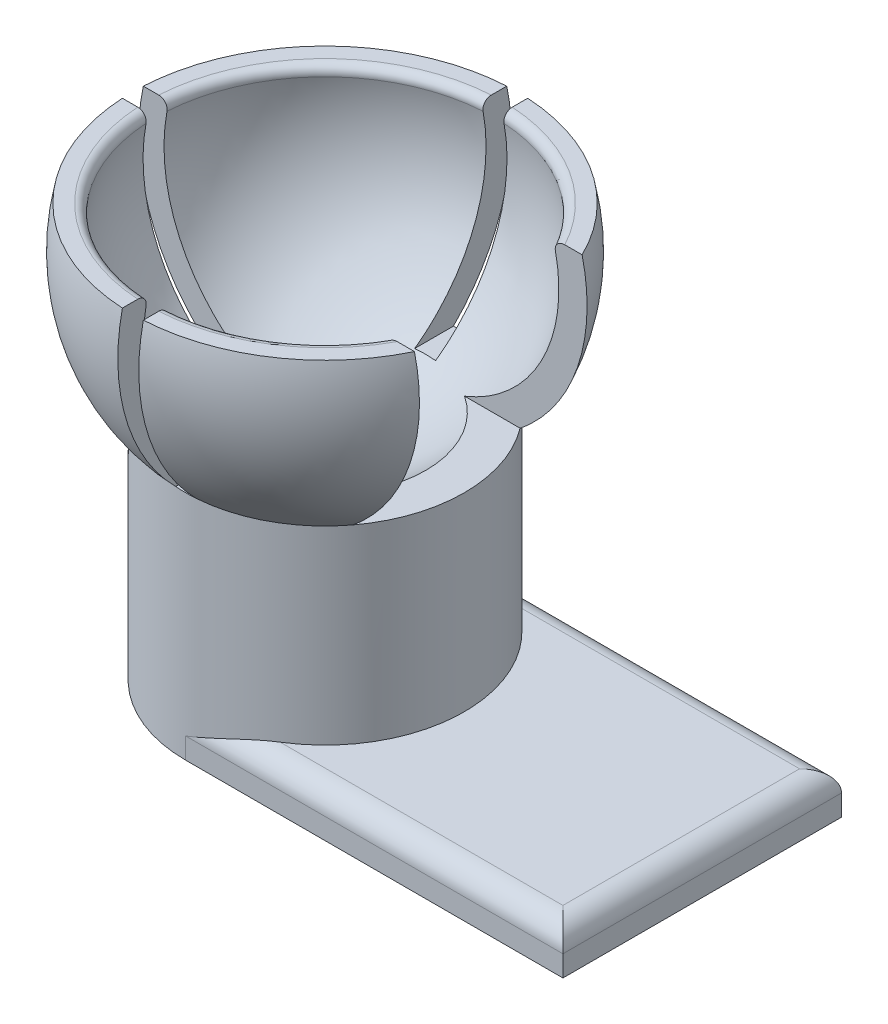
SolidWorks part; units mm, degrees
ref_plane "Front Plane" through (0, 0, 0) normal (0, 0, 1) x (1, 0, 0)
ref_plane "Top Plane" through (0, 0, 0) normal (0, 1, 0) x (1, 0, 0)
ref_plane "Right Plane" through (0, 0, 0) normal (1, 0, 0) x (0, 0, -1)
sketch "Sketch1" plane through (0, 0, 0) normal (0, 0, 1) x (1, 0, 0)
  line L0 (-9.1848, 2) -> (9.1848, 2)
  line L1 (0, 0) -> (0, 13.0891)
  line L2 (-6.6468, -6.6468) -> (-6.6468, -15.7)
  line L3 (-6.6468, -15.7) -> (6.6468, -15.7)
  line L4 (6.6468, -15.7) -> (6.6468, -6.6468)
  line L5 (0, 0) -> (6.6468, -6.6468) construction
  line L6 (0, 0) -> (-6.6468, -6.6468) construction
  circle A0 centre (0, 0) radius 8.2
  circle A1 centre (0, 0) radius 9.4
  dimension "D1" = 1.2
  dimension "D2" = 16.4
  dimension "D3" = 2
  dimension "D4" = 45
  dimension "D5" = 45
  dimension "D6" = 15.7
revolve "Revolve3" add sketch "Sketch1" angle 360 about L1 region at (-8.5686, 1.7801, 0) region at (0, -12.0774, 0)
sketch "Sketch2" plane through (0, 0, 0) normal (0, 0, 1) x (1, 0, 0)
  line L1 (-15.3435, 5.851) -> (17.0764, 5.851)
  line L2 (-15.3435, 5.851) -> (-15.3435, -6.6468)
  line L3 (-15.3435, -6.6468) -> (17.0764, -6.6468)
  line L4 (17.0764, 5.851) -> (17.0764, -6.6468)
extrude "Cut-Extrude1" cut sketch "Sketch2" against normal blind 0.5 and the other way blind 0.5
ref_axis "Axis1" through (0, 0, 0) along (0, 1, 0)
pattern_circular "CirPattern1" count 2 every 90 about axis through (0, 0, 0) along (0, 1, 0) of "Cut-Extrude1"
fillet "Fillet1" radius 0.4 4 edges at (5.6232, 2, -5.6232) (5.6232, 2, 5.6232) (-5.6232, 2, 5.6232) (-5.6232, 2, -5.6232)
sketch "Sketch3" plane through (0, 0, 0) normal (0, 0, 1) x (1, 0, 0)
  line L0 (0, -200000) -> (0, 200013.0891) construction
  line L1 (15.0884, 8.6675) -> (0, 8.6675)
  line L2 (15.0884, 8.6675) -> (15.0884, -6.6468)
  line L3 (15.0884, -6.6468) -> (0, -6.6468)
  line L4 (0, 8.6675) -> (0, -6.6468)
extrude "Cut-Extrude3" cut sketch "Sketch3" against normal blind 4 and the other way blind 4
sketch "Sketch4" plane through (0, -15.7, 0) normal (0, -1, 0) x (1, 0, 0)
  line L1 (0, 6.6468) -> (18, 6.6468)
  line L2 (0, 6.6468) -> (0, -6.6468)
  line L3 (0, -6.6468) -> (18, -6.6468)
  line L4 (18, 6.6468) -> (18, -6.6468)
  circle A0 centre (0, 0) radius 6.6468 construction
  circle M3 centre (0, 0) radius 6.6468
  dimension "D1" = 18
extrude "Boss-Extrude1" add sketch "Sketch4" along normal blind 3 contours L2 M3 | L4 L1 L3 M3 | L2 M3 region at (2.821, -15.7, 0) region at (11.5241, -15.7, 0) region at (-2.821, -15.7, 0)
chamfer "Chamfer1" distance 1 angle 45 4 edges at (18, -18.7, 0) (9, -18.7, 6.6468) (-6.6468, -18.7, 0) (9, -18.7, -6.6468)
fillet "Fillet2" radius 1 3 edges at (18, -15.7, 0)
